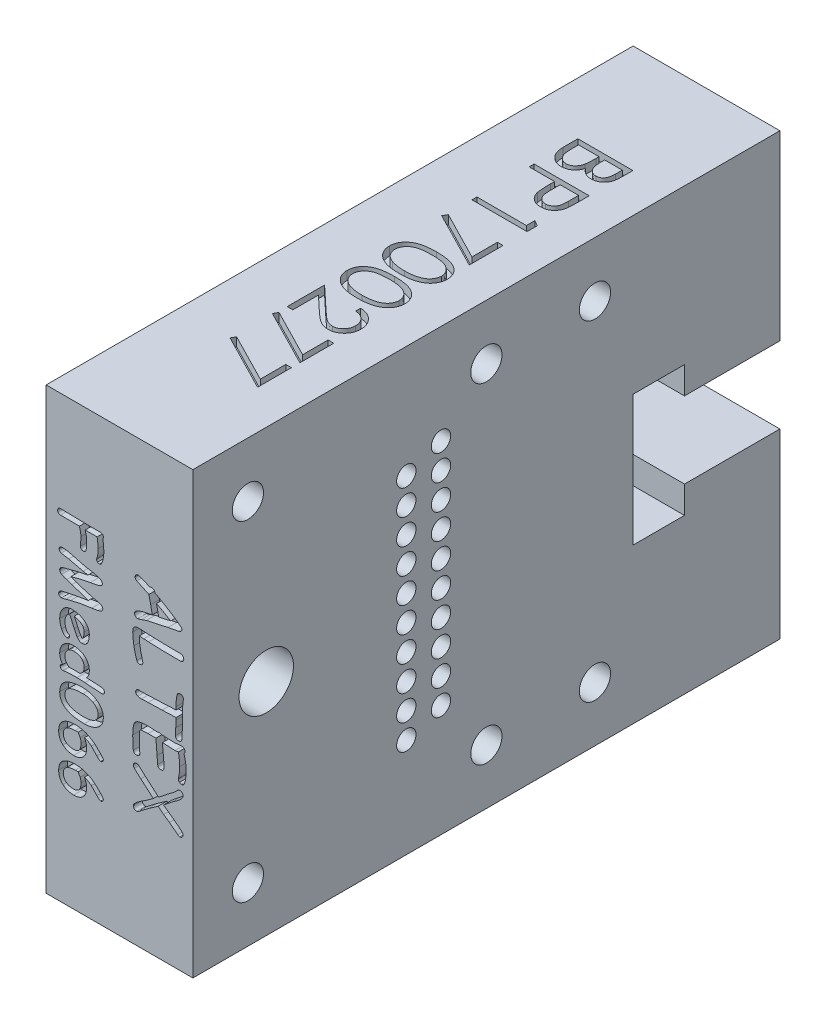
SolidWorks part; units mm, degrees
ref_plane "Front Plane" through (0, 0, 0) normal (1, 0, 0) x (0, 1, 0)
ref_plane "Top Plane" through (0, 0, 0) normal (0, 0, 1) x (0, 1, 0)
ref_plane "Right Plane" through (0, 0, 0) normal (0, 1, 0) x (-1, 0, 0)
sketch "Sketch1" plane through (0, 0, 0) normal (1, 0, 0) x (0, 1, 0)
  line L1 (-19.05, -25.4) -> (19.05, -25.4)
  line L2 (-19.05, -25.4) -> (-19.05, 25.4)
  line L3 (-19.05, 25.4) -> (19.05, 25.4)
  line L4 (19.05, -25.4) -> (19.05, 25.4)
  line L5 (-19.05, -25.4) -> (19.05, 25.4) construction
  line L6 (-19.05, 25.4) -> (19.05, -25.4) construction
  point P0 (0, 0)
  dimension "D1" = 38.1
  dimension "D2" = 50.8
extrude "Boss-Extrude1" add sketch "Sketch1" along normal blind 12.7
sketch "Sketch2" plane through (12.7, 0, 0) normal (1, 0, 0) x (0, 1, 0)
  line L0 (0, -25.4) -> (0, -12.7) construction
  line L1 (-19.05, -25.4) -> (19.05, -25.4) construction
  line L2 (3.302, -17.145) -> (5.6515, -17.145)
  line L3 (-5.6515, -12.7) -> (5.6515, -12.7)
  line L4 (-5.6515, -12.7) -> (-5.6515, -17.145)
  line L5 (-5.6515, -17.145) -> (-3.302, -17.145)
  line L6 (5.6515, -12.7) -> (5.6515, -17.145)
  line L8 (-3.302, -17.145) -> (-3.302, -25.4)
  line L9 (-3.302, -25.4) -> (3.302, -25.4)
  line L10 (3.302, -17.145) -> (3.302, -25.4)
  dimension "D1" = 12.7
  dimension "D2" = 6.604
  dimension "D3" = 3.302
  dimension "D4" = 4.445
  dimension "D5" = 5.6515
  dimension "D6" = 11.303
extrude "Cut-Extrude1" cut sketch "Sketch2" against normal up to vertex (12.7 mm away) up to point (0, 19.05, -25.4)
sketch "Sketch3" plane through (0, 0, 0) normal (-1, 0, 0) x (0, -1, 0)
  line L0 (-9.8, 6.56) -> (-8.9, 7.3) construction
  line L1 (-8.9, 7.3) -> (-7.6, 7.3) construction
  line L2 (-7.6, 7.3) -> (-6.7, 6.56) construction
  line L3 (-6.7, 6.56) -> (-5.4, 7.3) construction
  line L4 (-5.4, 7.3) -> (-4.5, 6.56) construction
  line L5 (-4.5, 6.56) -> (-3.2, 7.3) construction
  line L6 (-3.2, 7.3) -> (-2.3, 6.56) construction
  line L7 (-2.3, 6.56) -> (-1, 7.3) construction
  line L8 (-1, 7.3) -> (-0.1, 6.56) construction
  line L9 (-0.1, 6.56) -> (1.2, 7.3) construction
  line L10 (1.2, 7.3) -> (2.1, 6.56) construction
  line L11 (3.4, 7.3) -> (4.3, 6.56) construction
  line L12 (4.3, 6.56) -> (5.6, 7.3) construction
  line L13 (5.6, 7.3) -> (6.5, 6.56) construction
  line L14 (6.5, 6.56) -> (7.8, 7.3) construction
  line L15 (7.8, 7.3) -> (8.7, 6.56) construction
  line L16 (8.7, 6.56) -> (10, 7.3) construction
  line L17 (10, 7.3) -> (10.9, 6.56) construction
  line L18 (10.9, 6.56) -> (9.8, 4.3) construction
  line L19 (9.8, 4.3) -> (8.9, 3.56) construction
  line L20 (8.9, 3.56) -> (7.6, 3.56) construction
  line L21 (7.6, 3.56) -> (6.7, 4.3) construction
  line L22 (6.7, 4.3) -> (5.4, 4.3) construction
  line L23 (5.4, 4.3) -> (4.5, 3.56) construction
  line L24 (4.5, 3.56) -> (3.2, 4.3) construction
  line L25 (3.2, 4.3) -> (2.3, 3.56) construction
  line L26 (2.3, 3.56) -> (1, 4.3) construction
  line L27 (1, 4.3) -> (0.1, 3.56) construction
  line L28 (0.1, 3.56) -> (-1.2, 3.56) construction
  line L29 (-1.2, 3.56) -> (-2.1, 4.3) construction
  line L30 (-2.1, 4.3) -> (-3.4, 4.3) construction
  line L31 (-3.4, 4.3) -> (-4.3, 3.56) construction
  line L32 (-4.3, 3.56) -> (-5.6, 3.56) construction
  line L33 (-5.6, 3.56) -> (-6.5, 4.3) construction
  line L34 (-7.8, 4.3) -> (-8.7, 3.56) construction
  line L35 (-8.7, 3.56) -> (-10, 3.56) construction
  line L36 (-10, 3.56) -> (-10.9, 4.3) construction
  circle A0 centre (-8.25, 3.93) radius 0.8382
  circle A1 centre (-10.45, 3.93) radius 0.8382
  circle A2 centre (-6.05, 3.93) radius 0.8382
  circle A3 centre (-3.85, 3.93) radius 0.8382
  circle A4 centre (-1.65, 3.93) radius 0.8382
  circle A5 centre (0.55, 3.93) radius 0.8382
  circle A6 centre (2.75, 3.93) radius 0.8382
  circle A7 centre (4.95, 3.93) radius 0.8382
  circle A8 centre (7.15, 3.93) radius 0.8382
  circle A9 centre (9.35, 3.93) radius 0.8382
  circle A10 centre (10.45, 6.93) radius 0.8382
  circle A11 centre (8.25, 6.93) radius 0.8382
  circle A12 centre (6.05, 6.93) radius 0.8382
  circle A13 centre (3.85, 6.93) radius 0.8382
  circle A14 centre (1.65, 6.93) radius 0.8382
  circle A15 centre (-0.55, 6.93) radius 0.8382
  circle A16 centre (-2.75, 6.93) radius 0.8382
  circle A17 centre (-4.95, 6.93) radius 0.8382
  circle A18 centre (-7.15, 6.93) radius 0.8382
  circle A19 centre (-9.35, 6.93) radius 0.8382
  dimension "D1" = 1.6764
  dimension "D2" = 1.6764
sketch "Sketch6" plane through (0, 0, 25.4) normal (0, 0, 1) x (1, 0, 0)
  line L0 (7.7518, 12.7) -> (7.7518, -12.7) construction
  text T0 "ALTEX" font "Comic Sans MS" height in points 16
extrude "Cut-Extrude4" cut sketch "Sketch6" against normal blind 0.762
sketch "Sketch7" plane through (0, -19.05, 0) normal (0, -1, 0) x (1, 0, 0)
  line L0 (6.35, 25.4) -> (6.35, -25.4) construction
  line L1 (12.7, -25.4) -> (0, -25.4) construction
  line L2 (12.7, 25.4) -> (0, 25.4) construction
  text T0 "MX34020SF1" font "Century Gothic" height in points 18
extrude "Cut-Extrude5" cut sketch "Sketch7" against normal blind 0.762
sketch "Sketch8" plane through (0, 19.05, 0) normal (0, 1, 0) x (-1, 0, 0)
  line L0 (-4.5604, -25.4) -> (-4.5604, 25.4) construction
  line L1 (-12.7, -25.4) -> (0, -25.4) construction
  line L2 (-12.7, 25.4) -> (0, 25.4) construction
  text T0 "BP1700277" font "Century Gothic" height in points 18
extrude "Cut-Extrude6" cut sketch "Sketch8" against normal blind 0.762
sketch "Sketch9" plane through (0, 0, 25.4) normal (0, 0, 1) x (1, 0, 0)
  line L0 (1.2659, 19.05) -> (1.2659, -19.05) construction
  line L1 (12.7, 19.05) -> (0, 19.05) construction
  line L2 (12.7, -19.05) -> (0, -19.05) construction
  text T0 "FMed066" font "Comic Sans MS" height in points 14
extrude "Cut-Extrude7" cut sketch "Sketch9" against normal blind 0.762
sketch "Sketch10" plane through (12.7, 0, 0) normal (1, 0, 0) x (0, 1, 0)
  line L0 (-19.05, 25.4) -> (-19.05, -25.4) construction
  line L1 (-14.2875, 17.4113) -> (-11.4935, 19.0244)
  line L2 (-11.4935, 19.0244) -> (-11.4935, 22.2506)
  line L3 (-11.4935, 22.2506) -> (-14.2875, 23.8637)
  line L4 (-14.2875, 23.8637) -> (-17.0815, 22.2506)
  line L5 (-17.0815, 22.2506) -> (-17.0815, 19.0244)
  line L6 (-17.0815, 19.0244) -> (-14.2875, 17.4113)
  line L7 (14.2875, 17.4113) -> (17.0815, 19.0244)
  line L8 (17.0815, 19.0244) -> (17.0815, 22.2506)
  line L9 (17.0815, 22.2506) -> (14.2875, 23.8637)
  line L10 (14.2875, 23.8637) -> (11.4935, 22.2506)
  line L11 (11.4935, 22.2506) -> (11.4935, 19.0244)
  line L12 (11.4935, 19.0244) -> (14.2875, 17.4113)
  line L13 (19.05, -25.4) -> (19.05, 25.4) construction
  line L14 (19.05, 25.4) -> (-19.05, 25.4) construction
  line L15 (-19.05, -25.4) -> (-3.302, -25.4) construction
  line L16 (-11.0613, -9.398) -> (-12.6744, -6.604)
  line L17 (-12.6744, -6.604) -> (-15.9006, -6.604)
  line L18 (-15.9006, -6.604) -> (-17.5137, -9.398)
  line L19 (-17.5137, -9.398) -> (-15.9006, -12.192)
  line L20 (-15.9006, -12.192) -> (-12.6744, -12.192)
  line L21 (-12.6744, -12.192) -> (-11.0613, -9.398)
  line L22 (17.5137, -9.398) -> (15.9006, -6.604)
  line L23 (15.9006, -6.604) -> (12.6744, -6.604)
  line L24 (12.6744, -6.604) -> (11.0613, -9.398)
  line L25 (11.0613, -9.398) -> (12.6744, -12.192)
  line L26 (12.6744, -12.192) -> (15.9006, -12.192)
  line L27 (15.9006, -12.192) -> (17.5137, -9.398)
  circle A0 centre (-14.2875, 20.6375) radius 2.794 construction
  circle A1 centre (14.2875, 20.6375) radius 2.794 construction
  circle A2 centre (-14.2875, -9.398) radius 2.794 construction
  circle A3 centre (14.2875, -9.398) radius 2.794 construction
  dimension "D1" = 5.588
  dimension "D2" = 5.588
  dimension "D3" = 4.7625
  dimension "D4" = 4.7625
  dimension "D5" = 4.7625
  dimension "D7" = 5.588
  dimension "D8" = 5.588
  dimension "D11" = 13.208
hole_wizard "#6-32 Tapped Hole1" positions "Sketch11" profile "Sketch12" tap size "#6-32" standard "ANSI Inch" end condition up to next
sketch "Sketch11" plane through (12.7, 0, 0) normal (1, 0, 0) x (0, 1, 0)
  line L2 (-19.05, -25.4) -> (-3.302, -25.4) construction
  line L3 (3.302, -25.4) -> (19.05, -25.4) construction
  line L4 (19.05, 25.4) -> (-19.05, 25.4) construction
  line L6 (0, 25.4) -> (0, -28.4567) construction
  point P0 (-14.2875, 20.6375)
  point P3 (14.2875, 20.6375)
  point P6 (14.2875, -9.398)
  point P9 (-14.2875, -9.398)
  point P12 (-14.2875, 0)
  point P14 (14.2875, 0)
  point P16 (0, 19.05)
  dimension "D3" = 25.4
  dimension "D4" = 25.4
  dimension "D5" = 6.35
sketch "Sketch12" plane through (12.7, -14.2875, 20.6375) normal (0, 1, 0) x (0, 0, -1)
  line L0 (0, 0) -> (0, 12.7)
  line L1 (0, 12.7) -> (1.3525, 12.7)
  line L2 (1.3525, 12.7) -> (1.3525, 0)
  line L5 (1.3525, 0) -> (0, 0)
  line L11 (0, -6.35) -> (0, 107.95) construction
  dimension "Thru Tap Drill Dia." = 2.7051
  dimension "Thru Tap Drill Depth" = 12.7
cosmetic thread "Hole Thread1" parameters "D2"=3.5052
cosmetic thread "Hole Thread2" parameters "D2"=3.5052
cosmetic thread "Hole Thread3" parameters "D2"=3.5052
cosmetic thread "Hole Thread4" parameters "D2"=3.5052
cosmetic thread "Hole Thread5" parameters "D2"=3.5052
cosmetic thread "Hole Thread6" parameters "D2"=3.5052
cosmetic thread "Hole Thread7" parameters "D2"=3.5052
extrude "Cut-Extrude8" cut sketch "Sketch3" against normal up to vertex (12.7 mm away) up to point (12.7, 19.05, 25.4)
sketch "Sketch13" plane through (0, 0, 0) normal (-1, 0, 0) x (0, -1, 0)
  circle A0 centre (0, 19.05) radius 2.699
extrude "Boss-Extrude2" add sketch "Sketch13" against normal blind 6.35
sketch "Sketch14" plane through (6.35, 0, 0) normal (1, 0, 0) x (0, 1, 0)
  circle A0 centre (0, 19.05) radius 2.3544
extrude "Cut-Extrude9" cut sketch "Sketch14" along normal up to vertex (6.35 mm away) up to point (12.7, -19.05, 25.4)
